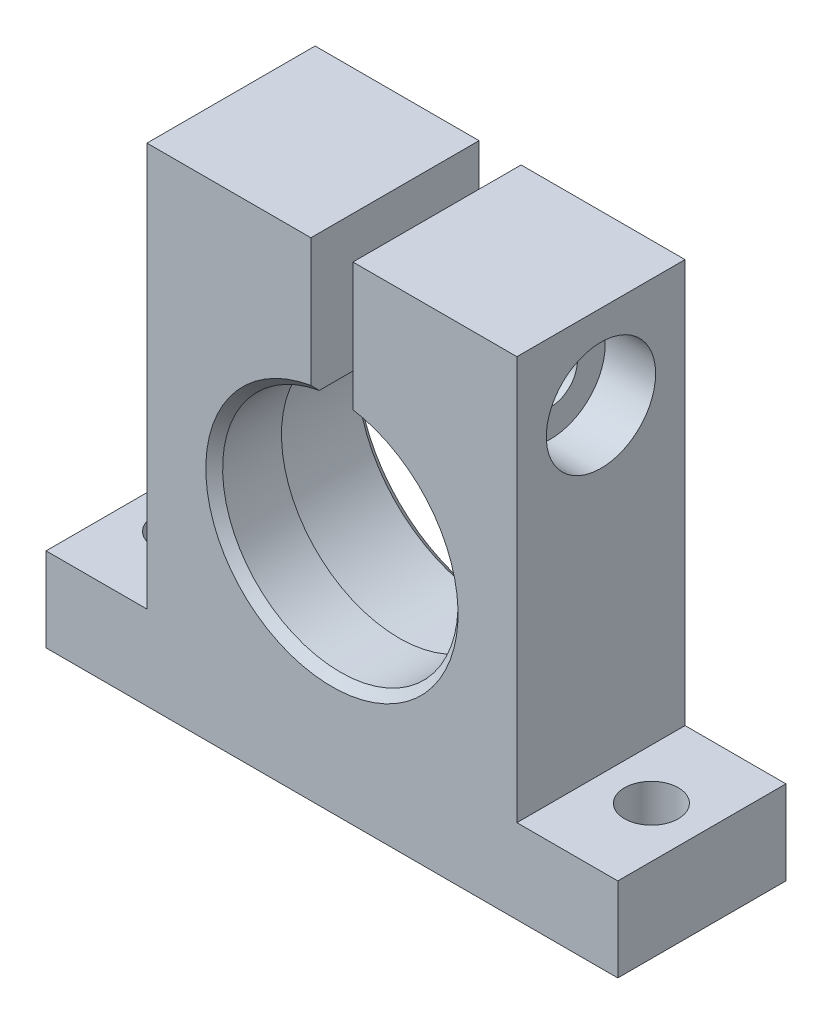
SolidWorks part; units mm, degrees
material "AISI 1045 Steel, cold drawn"
ref_plane "Front Plane" through (0, 0, 0) normal (0, 0, 1) x (1, 0, 0)
ref_plane "Top Plane" through (0, 0, 0) normal (0, 1, 0) x (1, 0, 0)
ref_plane "Right Plane" through (0, 0, 0) normal (1, 0, 0) x (0, 0, -1)
sketch "Sketch1" plane through (0, 0, 0) normal (0, 0, 1) x (1, 0, 0)
  line L1 (11, -14) -> (-11, -14)
  line L2 (11, -14) -> (11, 15)
  line L3 (11, 15) -> (-11, 15)
  line L4 (-11, -14) -> (-11, 15)
  line L5 (11, -14) -> (-11, 15) construction
  line L6 (11, 15) -> (-11, -14) construction
  circle A0 centre (0, 0) radius 8 construction
  point P3 (0, 0.5)
  dimension "D1" = 16
  dimension "D2" = 29
  dimension "D3" = 15
  dimension "D4" = 22
extrude "Boss-Extrude1" add sketch "Sketch1" along normal mid plane 10
sketch "Sketch3" plane through (0, -14, 0) normal (0, -1, 0) x (1, 0, 0)
  line L0 (-11, 5) -> (11, 5) construction
  line L1 (17, -5) -> (-17, -5)
  line L2 (17, -5) -> (17, 5)
  line L3 (17, 5) -> (-17, 5)
  line L4 (-17, -5) -> (-17, 5)
  line L5 (17, -5) -> (-17, 5) construction
  line L6 (17, 5) -> (-17, -5) construction
  point P0 (0, 0)
  dimension "D1" = 34
extrude "Boss-Extrude2" add sketch "Sketch3" against normal blind 5
hole_wizard "Ø16.0 (16) Diameter Hole1" positions "Sketch4" profile "Sketch5" hole size "Ø16.0" standard "ANSI Metric"
sketch "Sketch4" plane through (0, 0, -5) normal (0, 0, -1) x (-1, 0, 0)
  point P0 (0, 0)
sketch "Sketch5" plane through (0, 0, -5) normal (1, 0, 0) x (0, 1, 0)
  line L0 (0, 0) -> (0, 6)
  line L1 (0, 6) -> (8, 6)
  line L2 (8, 6) -> (8, 0)
  line L5 (8, 0) -> (0, 0)
  line L10 (0, 6) -> (-8, 6) construction
  line L11 (0, -6.35) -> (0, 107.95) construction
  dimension "Hole Dia." = 16
  dimension "Hole Depth" = 6
  dimension "Drill Angle" = 180
hole_wizard "Ø14.0 (14) Diameter Hole1" positions "Sketch13" profile "Sketch14" hole size "Ø14.0" standard "ANSI Metric" end condition through all
sketch "Sketch13" plane through (0, 0, 1) normal (0, 0, -1) x (-1, 0, 0)
  point P0 (0, 0)
sketch "Sketch14" plane through (0, 0, 1) normal (1, 0, 0) x (0, 1, 0)
  line L0 (0, 0) -> (0, 4)
  line L1 (0, 4) -> (7, 4)
  line L2 (7, 4) -> (7, 0)
  line L5 (7, 0) -> (0, 0)
  line L11 (0, -6.35) -> (0, 107.95) construction
  dimension "Thru Hole Dia." = 14
  dimension "Thru Hole Depth" = 4
hole_wizard "M3 Clearance Hole1" positions "Sketch6" profile "Sketch7" hole size "M3" standard "ANSI Metric" end condition through all
sketch "Sketch6" plane through (0, -9, 0) normal (0, 1, 0) x (1, 0, 0)
  line L0 (-17, -5) -> (-11, 5) construction
  line L2 (17, -5) -> (11, 5) construction
  point P0 (-14, 0)
  point P2 (14, 0)
sketch "Sketch7" plane through (-14, -9, 0) normal (1, 0, 0) x (0, 0, 1)
  line L0 (0, 0) -> (0, 5)
  line L1 (0, 5) -> (1.6, 5)
  line L2 (1.6, 5) -> (1.6, 0)
  line L5 (1.6, 0) -> (0, 0)
  line L11 (0, -6.35) -> (0, 107.95) construction
  dimension "Thru Hole Dia." = 3.2
  dimension "Thru Hole Depth" = 5
sketch "Sketch12" plane through (0, 0, 5) normal (0, 0, 1) x (1, 0, 0)
  line L0 (11, 15) -> (-11, 15) construction
  line L1 (1.25, 6.8875) -> (-1.25, 6.8875)
  line L2 (1.25, 6.8875) -> (1.25, 15)
  line L3 (1.25, 15) -> (-1.25, 15)
  line L4 (-1.25, 6.8875) -> (-1.25, 15)
  line L5 (1.25, 6.8875) -> (-1.25, 15) construction
  line L6 (1.25, 15) -> (-1.25, 6.8875) construction
  circle A1 centre (0, 0) radius 7 construction
  point P0 (0, 10.9437)
  dimension "D1" = 2.5
extrude "Cut-Extrude1" cut sketch "Sketch12" against normal through all
hole_wizard "M3x0.5 Tapped Hole1" positions "Sketch8" profile "Sketch9" tap size "M3x0.5" standard "ANSI Metric" end condition up to next
sketch "Sketch8" plane through (-11, 0, 0) normal (-1, 0, 0) x (0, 0, 1)
  line L0 (5, 15) -> (-5, 15) construction
  point P0 (0, 10)
  dimension "D1" = 5
sketch "Sketch9" plane through (-11, 10, 0) normal (0, 1, 0) x (0, 0, 1)
  line L0 (0, 0) -> (0, 9.75)
  line L1 (0, 9.75) -> (1.25, 9.75)
  line L2 (1.25, 9.75) -> (1.25, 0)
  line L5 (1.25, 0) -> (0, 0)
  line L11 (0, -6.35) -> (0, 107.95) construction
  dimension "Thru Tap Drill Dia." = 2.5
  dimension "Thru Tap Drill Depth" = 9.75
cosmetic thread "Hole Thread1" parameters "D2"=3
hole_wizard "CBORE for M3 SHCS1" positions "Sketch10" profile "Sketch11" counterbore size "M3" standard "ANSI Metric" end condition up to next
sketch "Sketch10" plane through (11, 0, 0) normal (1, 0, 0) x (0, 0, -1)
  point P0 (0, 10)
sketch "Sketch11" plane through (11, 10, 0) normal (0, 1, 0) x (0, 0, -1)
  line L0 (0, 0) -> (0, 9.75)
  line L1 (0, 9.75) -> (1.6, 9.75)
  line L3 (1.6, 9.75) -> (1.6, 3)
  line L4 (1.6, 3) -> (3.25, 3)
  line L5 (3.25, 3) -> (3.25, 0)
  line L7 (3.25, 0) -> (0, 0)
  line L11 (0, -6.35) -> (0, 107.95) construction
  dimension "Thru Hole Dia." = 3.2
  dimension "Thru Hole Depth" = 9.75
  dimension "C'Bore Dia." = 6.5
  dimension "C'Bore Depth" = 3
chamfer "Chamfer1" distance 0.5 angle 45 3 edges at (0, -8, -5) (0, -7, 5) (-11, 10, 1.25)
